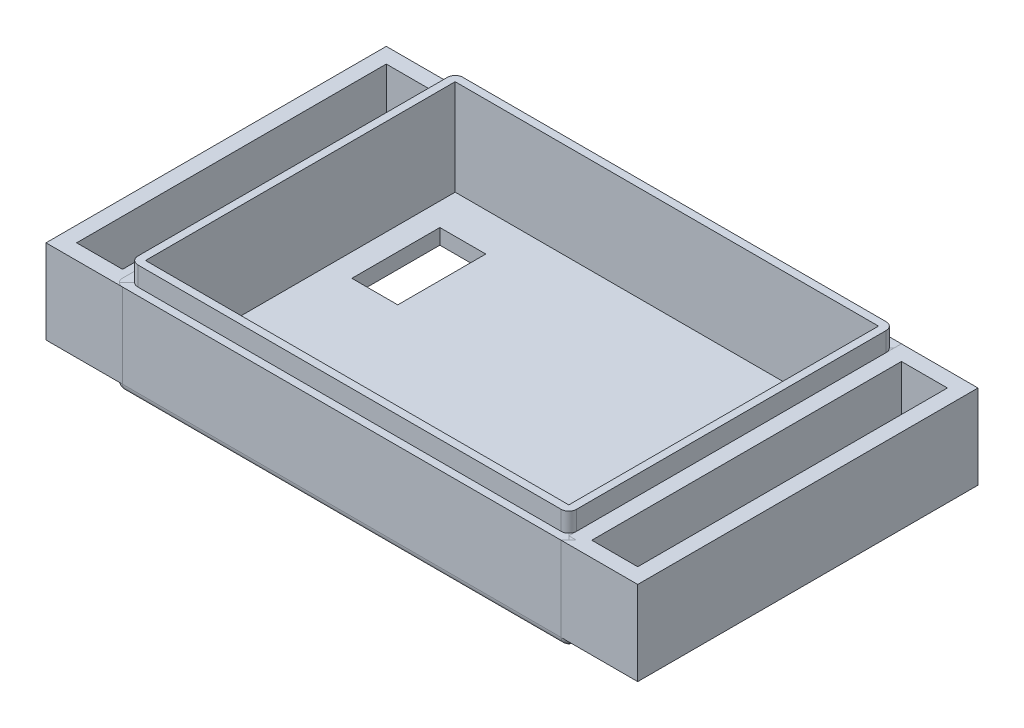
SolidWorks part; units mm, degrees
ref_plane "Front Plane" through (0, 0, 0) normal (0, 0, 1) x (1, 0, 0)
ref_plane "Top Plane" through (0, 0, 0) normal (0, 1, 0) x (1, 0, 0)
ref_plane "Right Plane" through (0, 0, 0) normal (1, 0, 0) x (0, 0, -1)
sketch "Sketch1" plane through (0, 0, 0) normal (0, 1, 0) x (1, 0, 0)
  line L1 (-29.655, 22.23) -> (29.655, 22.23)
  line L2 (-29.655, 22.23) -> (-29.655, -22.23)
  line L3 (-29.655, -22.23) -> (29.655, -22.23)
  line L4 (29.655, 22.23) -> (29.655, -22.23)
  dimension "D1" = 44.46
  dimension "D2" = 22.23
  dimension "D3" = 59.31
  dimension "D4" = 29.655
extrude "Boss-Extrude1" add sketch "Sketch1" along normal blind 2
sketch "Sketch2" plane through (0, 2, 0) normal (0, 1, 0) x (1, 0, 0)
  line L0 (27.655, -20.23) -> (27.655, 20.23)
  line L1 (27.655, 20.23) -> (-27.655, 20.23)
  line L2 (-27.655, 20.23) -> (-27.655, -20.23)
  line L3 (-27.655, -20.23) -> (27.655, -20.23)
  line L4 (-29.655, 22.23) -> (-29.655, -22.23)
  line L5 (-29.655, -22.23) -> (29.655, -22.23)
  line L6 (29.655, -22.23) -> (29.655, 22.23)
  line L7 (29.655, 22.23) -> (-29.655, 22.23)
  line L8 (-29.655, 22.23) -> (-29.655, -22.23)
  line L9 (-29.655, -22.23) -> (29.655, -22.23)
  line L10 (29.655, -22.23) -> (29.655, 22.23)
  line L11 (29.655, 22.23) -> (-29.655, 22.23)
  dimension "D1" = 0
  dimension "D2" = 2
extrude "Boss-Extrude2" add sketch "Sketch2" along normal blind 12.5
sketch "Sketch3" plane through (29.655, 0, 0) normal (1, 0, 0) x (0, 0, -1)
  line L1 (-21.23, 12) -> (-22.23, 12)
  line L2 (-21.23, 12) -> (-21.23, 14.5)
  line L3 (-21.23, 14.5) -> (-22.23, 14.5)
  line L4 (-22.23, 12) -> (-22.23, 14.5)
  dimension "D1" = 1
  dimension "D2" = 2.5
sketch "Sketch4" plane through (0, 14.5, 0) normal (0, 1, 0) x (1, 0, 0)
  line L0 (-29.655, -22.23) -> (29.655, -22.23) construction
  line L1 (-29.655, 22.23) -> (-29.655, -22.23) construction
  line L2 (29.655, 22.23) -> (-29.655, 22.23) construction
  line L3 (29.655, -22.23) -> (29.655, 22.23) construction
  line L4 (-29.655, -22.23) -> (29.655, -22.23)
  line L5 (-29.655, 22.23) -> (-29.655, -22.23)
  line L6 (29.655, 22.23) -> (-29.655, 22.23)
  line L7 (29.655, -22.23) -> (29.655, 22.23)
sweep "Cut-Sweep1" cut profiles "Sketch3" path "Sketch4"
fillet "Fillet1" radius 1 12 edges at (-29.655, 6, 22.23) (-29.655, 6, -22.23) (29.655, 6, -22.23) (-28.655, 13.25, -21.23) (28.655, 13.25, -21.23) (-28.655, 13.25, 21.23) (29.655, 0, 0) (0, 0, -22.23) (-29.655, 0, 0) (0, 0, 22.23)
sketch "Sketch5" plane through (0, 0, 0) normal (0, -1, 0) x (-1, 0, 0)
  line L0 (29.655, -21.23) -> (29.655, 21.23) construction
  line L1 (24.655, 3.73) -> (18.655, 3.73)
  line L2 (24.655, 3.73) -> (24.655, 15.23)
  line L3 (24.655, 15.23) -> (18.655, 15.23)
  line L4 (18.655, 3.73) -> (18.655, 15.23)
  line L5 (-27.655, 20.23) -> (27.655, 20.23) construction
  dimension "D1" = 11.5
  dimension "D2" = 6
  dimension "D3" = 5
  dimension "D4" = 5
extrude "Cut-Extrude1" cut sketch "Sketch5" against normal blind 10
sketch "Sketch6" plane through (0, 0, 0) normal (0, -1, 0) x (1, 0, 0)
  text T0 "A" font "Century Schoolbook" height in points 72
  dimension "D1" = 8
  dimension "D2" = 8
extrude "Boss-Extrude3" add sketch "Sketch6" along normal blind 2
sketch "Sketch7" plane through (0, 0, 0) normal (0, -1, 0) x (1, 0, 0)
  line L0 (-28.655, 20.23) -> (-28.655, -20.23) construction
  line L1 (28.655, -20.23) -> (28.655, 20.23) construction
  line L2 (-28.655, 20.23) -> (-28.655, -20.23)
  line L3 (28.655, -20.23) -> (28.655, 20.23)
  line L4 (-28.655, -20.23) -> (-28.655, -22.23)
  line L5 (-28.655, -22.23) -> (-38.655, -22.23)
  line L6 (-38.655, -22.23) -> (-38.655, 22.23)
  line L7 (-38.655, 22.23) -> (-28.655, 22.23)
  line L8 (-28.655, 22.23) -> (-28.655, 20.23)
  line L9 (28.655, -20.23) -> (28.655, -22.23)
  line L10 (28.655, -22.23) -> (38.6584, -22.23)
  line L11 (38.6584, -22.23) -> (38.6584, 22.23)
  line L12 (38.6584, 22.23) -> (28.655, 22.23)
  line L13 (28.655, 22.23) -> (28.655, 20.23)
  line L14 (-30.655, 20.23) -> (-30.655, -20.23)
  line L15 (-30.655, -20.23) -> (-30.655, -20.23)
  line L16 (-30.655, -20.23) -> (-36.655, -20.23)
  line L17 (-36.655, -20.23) -> (-36.655, 20.23)
  line L18 (-36.655, 20.23) -> (-30.655, 20.23)
  line L19 (-30.655, 20.23) -> (-30.655, 20.23)
  line L20 (36.6584, -20.23) -> (36.6584, 20.23)
  line L21 (36.6584, 20.23) -> (30.655, 20.23)
  line L22 (30.655, 20.23) -> (30.655, 20.23)
  line L23 (30.655, -20.23) -> (30.655, 20.23)
  line L24 (30.655, -20.23) -> (30.655, -20.23)
  line L25 (30.655, -20.23) -> (36.6584, -20.23)
  dimension "D1" = 10
  dimension "D2" = 10.0034
  dimension "D3" = 2
extrude "Boss-Extrude10" add sketch "Sketch7" against normal blind 11 from offset 1 separate body offset against normal yes
